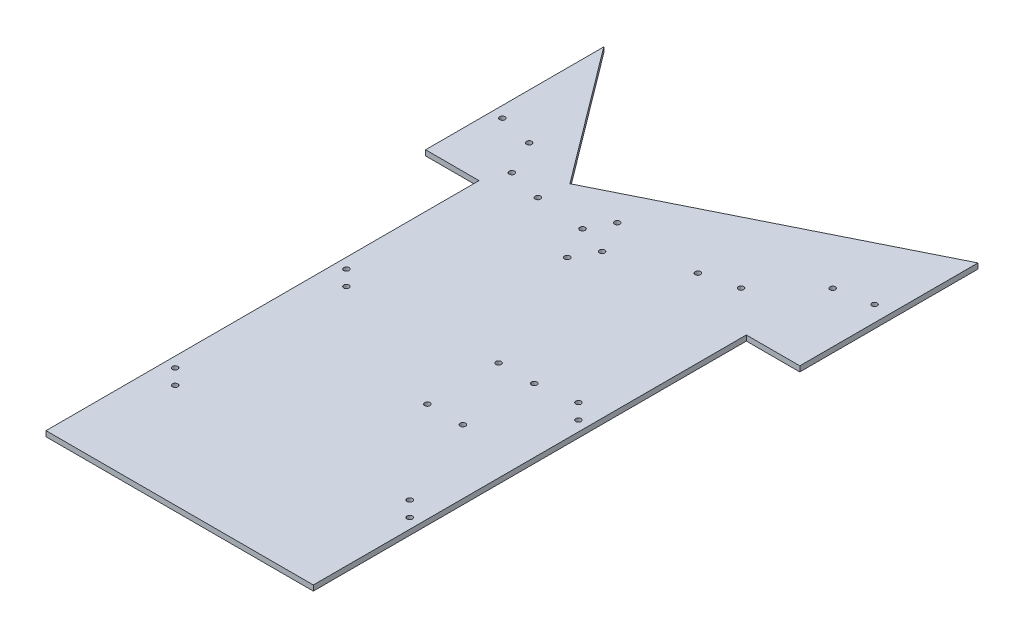
SolidWorks part; units mm, degrees
ref_plane "Front Plane" through (0, 0, 0) normal (0, 0, 1) x (1, 0, 0)
ref_plane "Top Plane" through (0, 0, 0) normal (0, 1, 0) x (1, 0, 0)
ref_plane "Right Plane" through (0, 0, 0) normal (1, 0, 0) x (0, 0, -1)
sketch "Sketch1" plane through (0, 0, 0) normal (0, 1, 0) x (1, 0, 0)
  line L1 (-75, -100) -> (75, -100)
  line L2 (-75, -100) -> (-75, 100)
  line L3 (-75, 100) -> (75, 100)
  line L4 (75, -100) -> (75, 100)
  line L5 (-75, -100) -> (75, 100) construction
  line L6 (-75, 100) -> (75, -100) construction
  circle A0 centre (-69.2426, 62.7961) radius 1.5
  circle A1 centre (-60.7574, 54.3108) radius 1.5
  circle A2 centre (60.7574, 63.0348) radius 1.5
  circle A3 centre (69.2426, 54.5495) radius 1.5
  circle A4 centre (-69.2426, -33.2742) radius 1.5
  circle A5 centre (-60.7574, -41.7595) radius 1.5
  circle A6 centre (60.7574, -31.6419) radius 1.5
  circle A7 centre (69.2426, -40.1271) radius 1.5
  circle A8 centre (19.1, 59.876) radius 1.5
  circle A10 centre (39.1, 19.876) radius 1.5
  circle A11 centre (19.1, 19.876) radius 1.5
  circle A12 centre (39.1, 59.876) radius 1.5
  point P0 (0, 0)
  dimension "D1" = 150
  dimension "D2" = 200
extrude "Boss-Extrude1" add sketch "Sketch1" along normal blind 3
sketch "Sketch2" plane through (0, 3, 0) normal (0, 1, 0) x (1, 0, 0)
  line L8 (-75, 100) -> (-75, 143)
  line L9 (-75, 143) -> (-105, 143)
  line L10 (-105, 143) -> (-105, 243)
  line L11 (-105, 243) -> (-48, 167)
  line L12 (-48, 167) -> (105, 243)
  line L13 (105, 243) -> (105, 143)
  line L14 (105, 143) -> (75, 143)
  line L15 (75, 143) -> (75, 100)
  line L20 (-75, 100) -> (75, 100)
  circle A0 centre (-12.8714, 130.3772) radius 1.5
  circle A1 centre (-6.0318, 143.0744) radius 1.5
  circle A2 centre (-15.7372, 161.3276) radius 1.5
  circle A3 centre (-22.5768, 148.6304) radius 1.5
  circle A4 centre (31.34, 159.4445) radius 1.5
  circle A5 centre (50.7426, 164.2965) radius 1.5
  circle A6 centre (76.5366, 189.8832) radius 1.5
  circle A7 centre (96.1557, 193.7679) radius 1.5
  circle A8 centre (-50.2701, 151.2364) radius 1.5
  circle A9 centre (-69.6726, 156.0884) radius 1.5
  circle A10 centre (-79.3212, 175.4165) radius 1.5
  circle A11 centre (-98.8125, 179.8985) radius 1.5
  dimension "D2" = 100
  dimension "D3" = 27
  dimension "D4" = 30
  dimension "D1" = 43
  dimension "D5" = 24
extrude "Boss-Extrude3" add sketch "Sketch2" against normal blind 3
